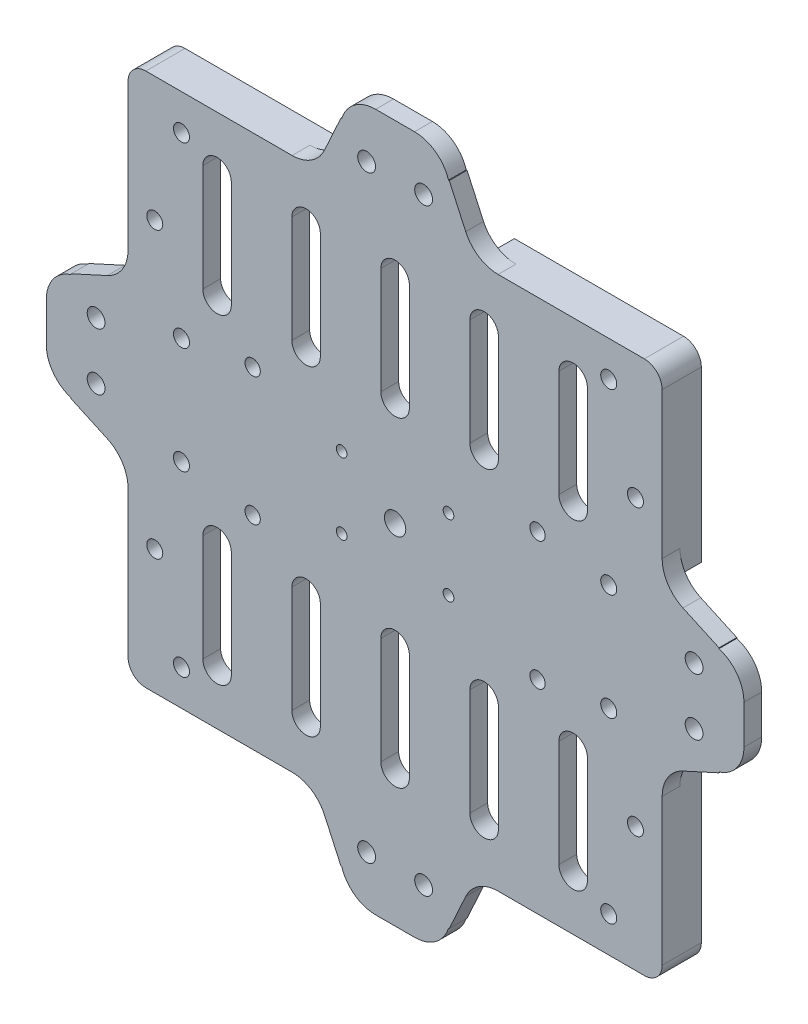
SolidWorks part; units mm, degrees
note: The reader was unsure of these and kept them because the rebuilt part matched: shared geometry of "Sketch1<4>".
material "ABS"
ref_plane "Front Plane" through (0, 0, 0) normal (0, 0, 1) x (1, 0, 0)
ref_plane "Top Plane" through (0, 0, 0) normal (0, 1, 0) x (1, 0, 0)
ref_plane "Right Plane" through (0, 0, 0) normal (1, 0, 0) x (0, 0, -1)
sketch "Sketch1" plane through (0, 0, 0) normal (0, 0, 1) x (1, 0, 0)
  line L13 (-90, -90) -> (90, -90)
  line L14 (-90, -90) -> (-90, 90)
  line L15 (-90, 90) -> (90, 90)
  line L16 (90, -90) -> (90, 90)
  line L17 (-90, -90) -> (90, 90) construction
  line L18 (-90, 90) -> (90, -90) construction
  line L19 (-75, -75) -> (75, -75)
  line L20 (-75, -75) -> (-75, 75)
  line L21 (-75, 75) -> (75, 75)
  line L22 (75, -75) -> (75, 75)
  line L23 (-75, -75) -> (75, 75) construction
  line L24 (-75, 75) -> (75, -75) construction
  line L39 (-75, -24.9122) -> (-75, 26.5574)
  line L40 (75, 22.5) -> (75, -22.5)
  line L41 (75, -22.5) -> (90.9698, -15.2063)
  line L42 (90.9698, -15.2063) -> (90.9698, 15.2063)
  line L43 (90.9698, 15.2063) -> (75, 22.5)
  line L44 (15.2063, -90.9698) -> (22.5, -75)
  line L45 (22.5, -75) -> (-22.5, -75)
  line L46 (-22.5, -75) -> (-15.2063, -90.9698)
  line L47 (-15.2063, -90.9698) -> (15.2063, -90.9698)
  line L48 (-90.9698, -15.2063) -> (-75, -22.5)
  line L49 (-75, -22.5) -> (-75, 22.5)
  line L50 (-75, 22.5) -> (-90.9698, 15.2063)
  line L51 (-90.9698, 15.2063) -> (-90.9698, -15.2063)
  line L52 (-15.2063, 90.9698) -> (-22.5, 75)
  line L53 (-22.5, 75) -> (22.5, 75)
  line L54 (22.5, 75) -> (15.2063, 90.9698)
  line L55 (15.2063, 90.9698) -> (-15.2063, 90.9698)
  line L64 (-72, -72) -> (-72, 72)
  line L65 (-72, 72) -> (72, 72)
  line L70 (72, -72) -> (72, 72)
  line L71 (-72, -72) -> (72, -72)
  line L72 (-10.5, -75) -> (10.5, -75)
  line L77 (75, -10.5) -> (64, -10.5)
  line L78 (75, -10.5) -> (75, 10.5)
  line L79 (75, 10.5) -> (64, 10.5)
  line L80 (64, -10.5) -> (64, 10.5)
  line L81 (-10.5, -75) -> (-10.5, -64)
  line L82 (-10.5, -64) -> (10.5, -64)
  line L83 (10.5, -75) -> (10.5, -64)
  line L84 (-75, 10.5) -> (-75, -10.5)
  line L85 (-75, 10.5) -> (-64, 10.5)
  line L86 (-64, 10.5) -> (-64, -10.5)
  line L87 (-75, -10.5) -> (-64, -10.5)
  line L88 (10.5, 75) -> (-10.5, 75)
  line L89 (10.5, 75) -> (10.5, 64)
  line L90 (10.5, 64) -> (-10.5, 64)
  line L91 (-10.5, 75) -> (-10.5, 64)
  line L92 (-75, 45) -> (-72, 45)
  line L93 (-45, 75) -> (-45, 72)
  line L94 (-75, 22.5) -> (-72, 22.5)
  line L95 (-75, -22.5) -> (-72, -22.5)
  line L96 (-22.5, 75) -> (-22.5, 72)
  line L97 (22.5, 75) -> (22.5, 72)
  line L98 (75, 22.5) -> (72, 22.5)
  line L99 (75, -22.5) -> (72, -22.5)
  line L100 (22.5, -75) -> (22.5, -72)
  line L101 (-22.5, -75) -> (-22.5, -72)
  circle A0 centre (83.9698, 8) radius 2.5
  circle A2 centre (83.9698, -8) radius 2.5
  circle A3 centre (8, -83.9698) radius 2.5
  circle A5 centre (-8, -83.9698) radius 2.5
  circle A6 centre (-83.9698, -8) radius 2.5
  circle A8 centre (-83.9698, 8) radius 2.5
  circle A9 centre (-8, 83.9698) radius 2.5
  circle A11 centre (8, 83.9698) radius 2.5
  circle A12 centre (0, 0) radius 3
  point P0 (0, 0)
  point P11 (0, 0)
  point P85 (0, 0)
  dimension "D3" = 4
  dimension "D12" = 6
  dimension "D1" = 180
  dimension "D2" = 180
  dimension "D4" = 150
  dimension "D5" = 4
  dimension "D6" = 3
  dimension "D8" = 11
  dimension "D7" = 21
  dimension "D10" = 45
  dimension "D11" = 45
  dimension "D9" = 4
  dimension "D13" = 4
extrude "Boss-Extrude1" add sketch "Sketch1" along normal mid plane 5 contours L91 L65 L64 L85 L86 L87 L71 L81 L82 L83 L70 L77 L80 L79 L89 L90 A12 | L39 L49 L50 L14 L48 A8 A6 | L94 L39 L85 L64 | L20 L94 L64 L92 | L39 L95 L64 L87 | L19 L101 L71 L64 L95 L20 | L19 L46 L13 L44 L45 A5 A3 | L101 L19 L81 L71 | L45 L83 L71 L81 | L71 L83 L82 L81 | L19 L100 L71 L83 | L100 L19 L22 L99 L70 L71 | L46 L47 L44 L13 | L99 L22 L77 L70 | L16 L43 L22 L40 L41 A2 A0 | L42 L43 L16 L41 | L40 L79 L70 L77 | L80 L77 L70 L79 | L22 L98 L70 L79 | L98 L22 L21 L97 L65 L70 | L97 L21 L89 L65 | L21 L53 L54 L15 L52 A11 A9 | L21 L96 L65 L91 | L53 L91 L65 L89 | L54 L55 L52 L15 | L96 L21 L93 L65 | L65 L91 L90 L89 | L93 L21 L20 L92 L64 L65 | L64 L87 L86 L85 | L49 L87 L64 L85 | L50 L51 L48 L14
extrude "Boss-Extrude3" add sketch "Sketch1<4>" against normal blind 6 from surface contours L93 L21 L20 L92 L64 L65 | L87 L39 L20 L19 L81 L71 L64 | L21 L89 L65 L70 L79 L22 | L83 L19 L22 L77 L70 L71 | L21 L93 L65 L91 | L92 L20 L39 L85 L64
sketch "Sketch1<4>" plane through (0, 0, 0) normal (0, 0, 1) x (1, 0, 0) same geometry as "Sketch1"
sketch "Sketch6" plane through (0, 0, 0) normal (0, 0, 1) x (1, 0, 0)
  line L0 (-25, 60) -> (-25, 30) construction
  line L12 (-40, 18) -> (40, 18) construction
  line L14 (6.05, 0) -> (-6.05, 0) construction
  line L15 (-40, -18) -> (40, -18) construction
  line L17 (-15, -10) -> (15, -10) construction
  line L18 (-15, -10) -> (-15, 10) construction
  line L19 (-15, 10) -> (15, 10) construction
  line L20 (15, -10) -> (15, 10) construction
  line L21 (-15, -10) -> (15, 10) construction
  line L22 (-15, 10) -> (15, -10) construction
  line L23 (-50, 60) -> (-50, 30) construction
  line L24 (-46, 60) -> (-46, 30)
  line L25 (-54, 60) -> (-54, 30)
  line L26 (-21, 60) -> (-21, 30)
  line L29 (-29, 60) -> (-29, 30)
  line L30 (0, 60) -> (0, 30) construction
  line L31 (4, 60) -> (4, 30)
  line L32 (-4, 60) -> (-4, 30)
  line L33 (25, 60) -> (25, 30) construction
  line L34 (29, 60) -> (29, 30)
  line L35 (21, 60) -> (21, 30)
  line L36 (50, 60) -> (50, 30) construction
  line L37 (54, 60) -> (54, 30)
  line L38 (46, 60) -> (46, 30)
  line L39 (116.8959, 0) -> (-116.8959, 0) construction
  line L40 (-50, -60) -> (-50, -30) construction
  line L41 (-46, -60) -> (-46, -30)
  line L42 (-54, -60) -> (-54, -30)
  line L43 (-25, -60) -> (-25, -30) construction
  line L44 (-21, -60) -> (-21, -30)
  line L45 (-29, -60) -> (-29, -30)
  line L46 (0, -60) -> (0, -30) construction
  line L47 (4, -60) -> (4, -30)
  line L48 (-4, -60) -> (-4, -30)
  line L49 (25, -60) -> (25, -30) construction
  line L50 (29, -60) -> (29, -30)
  line L51 (21, -60) -> (21, -30)
  line L52 (50, -60) -> (50, -30) construction
  line L53 (54, -60) -> (54, -30)
  line L54 (46, -60) -> (46, -30)
  circle A8 centre (40, 18) radius 2.15
  circle A9 centre (-40, 18) radius 2.15
  circle A10 centre (40, -18) radius 2.15
  circle A11 centre (-40, -18) radius 2.15
  circle A12 centre (-15, 10) radius 1.5
  circle A13 centre (-15, -10) radius 1.5
  circle A14 centre (15, -10) radius 1.5
  circle A15 centre (15, 10) radius 1.5
  arc A16 (-46, 60) -> (-54, 60) centre (-50, 60) ccw
  arc A17 (-54, 30) -> (-46, 30) centre (-50, 30) ccw
  arc A20 (-21, 60) -> (-29, 60) centre (-25, 60) ccw
  arc A21 (-29, 30) -> (-21, 30) centre (-25, 30) ccw
  arc A22 (4, 60) -> (-4, 60) centre (0, 60) ccw
  arc A23 (-4, 30) -> (4, 30) centre (0, 30) ccw
  arc A24 (29, 60) -> (21, 60) centre (25, 60) ccw
  arc A25 (21, 30) -> (29, 30) centre (25, 30) ccw
  arc A26 (54, 60) -> (46, 60) centre (50, 60) ccw
  arc A27 (46, 30) -> (54, 30) centre (50, 30) ccw
  arc A28 (-46, -60) -> (-54, -60) centre (-50, -60) cw
  arc A29 (-54, -30) -> (-46, -30) centre (-50, -30) cw
  arc A30 (-21, -60) -> (-29, -60) centre (-25, -60) cw
  arc A31 (-29, -30) -> (-21, -30) centre (-25, -30) cw
  arc A32 (4, -60) -> (-4, -60) centre (0, -60) cw
  arc A33 (-4, -30) -> (4, -30) centre (0, -30) cw
  arc A34 (29, -60) -> (21, -60) centre (25, -60) cw
  arc A35 (21, -30) -> (29, -30) centre (25, -30) cw
  arc A36 (54, -60) -> (46, -60) centre (50, -60) cw
  arc A37 (46, -30) -> (54, -30) centre (50, -30) cw
  point P3 (-25, 45)
  point P10 (0, 45)
  point P17 (25, 45)
  point P24 (50, 45)
  point P32 (0, 18)
  point P41 (0, 0)
  point P51 (-50, 45)
  point P60 (-50, -45)
  point P67 (-25, -45)
  point P74 (0, -45)
  point P81 (25, -45)
  point P88 (50, -45)
  dimension "D13" = 4.3
  dimension "D14" = 4.3
  dimension "D17" = 3
  dimension "D9" = 30
  dimension "D3" = 5
  dimension "D4" = 45
  dimension "D5" = 8
  dimension "D7" = 50
  dimension "D15" = 80
  dimension "D16" = 18
  dimension "D21" = 30
  dimension "D22" = 20
extrude "Cut-Extrude3" cut sketch "Sketch6" against normal mid plane 10
sketch "Sketch7" plane through (0, 0, 0) normal (0, 0, 1) x (1, 0, 0)
  line L0 (-90.9698, 15.2063) -> (-90.9698, -15.2063) construction
  line L1 (-97.9698, -15) -> (-90.9698, -15)
  line L2 (-97.9698, -15) -> (-97.9698, 15)
  line L3 (-97.9698, 15) -> (-90.9698, 15)
  line L4 (-90.9698, -15) -> (-90.9698, 15)
  line L5 (-97.9698, -15) -> (-90.9698, 15) construction
  line L6 (-97.9698, 15) -> (-90.9698, -15) construction
  line L7 (97.9698, -15) -> (90.9698, -15)
  line L8 (97.9698, -15) -> (97.9698, 15)
  line L9 (97.9698, 15) -> (90.9698, 15)
  line L10 (90.9698, -15) -> (90.9698, 15)
  line L11 (97.9698, -15) -> (90.9698, 15) construction
  line L12 (97.9698, 15) -> (90.9698, -15) construction
  line L17 (15.2063, 90.9698) -> (-15.2063, 90.9698) construction
  line L18 (-15, 97.9698) -> (15, 97.9698)
  line L19 (-15, 97.9698) -> (-15, 90.9698)
  line L20 (-15, 90.9698) -> (15, 90.9698)
  line L21 (15, 97.9698) -> (15, 90.9698)
  line L22 (-15, 97.9698) -> (15, 90.9698) construction
  line L23 (-15, 90.9698) -> (15, 97.9698) construction
  line L24 (15, -97.9698) -> (-15, -97.9698)
  line L25 (15, -97.9698) -> (15, -90.9698)
  line L26 (15, -90.9698) -> (-15, -90.9698)
  line L27 (-15, -97.9698) -> (-15, -90.9698)
  line L28 (15, -97.9698) -> (-15, -90.9698) construction
  line L29 (15, -90.9698) -> (-15, -97.9698) construction
  line L30 (90.9698, -15.2063) -> (90.9698, 15.2063) construction
  line L31 (-15.2063, -90.9698) -> (15.2063, -90.9698) construction
  point P0 (-94.4698, 0)
  point P6 (94.4698, 0)
  point P13 (0, -94.4698)
  point P17 (0, 94.4698)
  dimension "D1" = 7
  dimension "D2" = 30
  dimension "D3" = 7
  dimension "D4" = 7
  dimension "D5" = 7
  dimension "D6" = 30
  dimension "D7" = 30
  dimension "D8" = 30
extrude "Boss-Extrude4" add sketch "Sketch7" along normal up to surface (5 mm away) from surface at -2.5 contours L1 L4 L3 L2 | L21 L18 L19 L20 | L10 L7 L8 L9 | L27 L24 L25 L26 up to face at (25, -45, 2.5) starting at face at (25, -45, -2.5)
sketch "Sketch8" [suppressed] plane through (0, 0, 0) normal (0, 0, 1) x (1, 0, 0)
  line L0 (10.5, 75) -> (75, 75) construction
  line L1 (10.5, 72) -> (72, 72) construction
  line L2 (10.5, 75) -> (10.5, 72) construction
  line L3 (75, 10.5) -> (75, 75) construction
  line L4 (72, 10.5) -> (72, 72) construction
  line L5 (10.5, -75) -> (10.5, -72) construction
  line L6 (10.5, -72) -> (72, -72) construction
  line L7 (72, -72) -> (72, -10.5) construction
  line L8 (72, -10.5) -> (75, -10.5) construction
  line L9 (75, -10.5) -> (75, -75) construction
  line L10 (75, -75) -> (10.5, -75) construction
  line L11 (-75, -10.5) -> (-72, -10.5) construction
  line L12 (-72, -10.5) -> (-72, -72) construction
  line L13 (-72, -72) -> (-10.5, -72) construction
  line L14 (-10.5, -72) -> (-10.5, -75) construction
  line L15 (-10.5, -75) -> (-75, -75) construction
  line L16 (-75, -75) -> (-75, -10.5) construction
  line L17 (-72, 10.5) -> (-72, 72) construction
  line L18 (-75, 10.5) -> (-75, 75) construction
  line L19 (-10.5, 75) -> (-10.5, 72) construction
  line L20 (-72, 72) -> (-10.5, 72) construction
  line L21 (-75, 75) -> (-10.5, 75) construction
  line L22 (10.5, -75) -> (10.5, -72)
  line L23 (10.5, -72) -> (72, -72)
  line L24 (72, -72) -> (72, -10.5)
  line L25 (72, -10.5) -> (75, -10.5)
  line L26 (75, -10.5) -> (75, -75)
  line L27 (75, -75) -> (10.5, -75)
  line L28 (-75, -10.5) -> (-72, -10.5)
  line L29 (-72, -10.5) -> (-72, -72)
  line L30 (-72, -72) -> (-10.5, -72)
  line L31 (-10.5, -72) -> (-10.5, -75)
  line L32 (-10.5, -75) -> (-75, -75)
  line L33 (-75, -75) -> (-75, -10.5)
  line L34 (-72, 10.5) -> (-72, 72)
  line L35 (-75, 10.5) -> (-75, 75)
  line L36 (-10.5, 75) -> (-10.5, 72)
  line L37 (-72, 72) -> (-10.5, 72)
  line L38 (-75, 75) -> (-10.5, 75)
  line L39 (10.5, 75) -> (75, 75)
  line L40 (72, 10.5) -> (72, 72)
  line L41 (75, 10.5) -> (75, 75)
  line L42 (10.5, 75) -> (10.5, 72)
  line L43 (10.5, 72) -> (72, 72)
  line L44 (-75, 10.5) -> (-72, 10.5)
  line L45 (75, 10.5) -> (72, 10.5)
fillet "Fillet1" radius 10 16 edges at (22.5, -75, 0) (22.5, 75, 0) (75, 22.5, 0) (-75, -22.5, 0) (15, 97.9698, 0) (-15, 97.9698, 0) (-97.9698, 15, 0) (-97.9698, -15, 0) (-15, -97.9698, 0) (15, -97.9698, 0) (97.9698, -15, 0) (97.9698, 15, 0) (75, -22.5, 0) (-22.5, -75, 0) (-75, 22.5, 0) (-22.5, 75, 0)
fillet "Fillet2" [suppressed] radius 5
fillet "Fillet3" radius 5 4 edges at (75, 75, -3) (75, -75, -3) (-75, 75, -3) (-75, -75, -3)
sketch "Sketch9" plane through (0, 0, 0) normal (0, 0, 1) x (1, 0, 0)
  line L0 (67.5, 40) -> (-67.5, 40) construction
  line L1 (-60, 65) -> (60, 65) construction
  line L2 (-60, 65) -> (-60, 15) construction
  line L3 (-60, 15) -> (60, 15) construction
  line L4 (60, 65) -> (60, 15) construction
  line L5 (116.8959, 0) -> (-116.8959, 0) construction
  line L6 (-60, -65) -> (-60, -15) construction
  line L7 (-60, -15) -> (60, -15) construction
  line L8 (60, -65) -> (60, -15) construction
  line L9 (-60, -65) -> (60, -65) construction
  circle A0 centre (-60, 65) radius 2.25
  circle A1 centre (-60, 15) radius 2.25
  circle A2 centre (60, 15) radius 2.25
  circle A3 centre (60, 65) radius 2.25
  circle A4 centre (67.5, 40) radius 2.25
  circle A5 centre (-67.5, 40) radius 2.25
  circle A6 centre (-60, -15) radius 2.25
  circle A7 centre (60, -15) radius 2.25
  circle A8 centre (-60, -65) radius 2.25
  circle A9 centre (-67.5, -40) radius 2.25
  circle A10 centre (60, -65) radius 2.25
  circle A11 centre (67.5, -40) radius 2.25
  point P8 (0, 65)
  point P16 (-60, 40)
  point P17 (0, 40)
  dimension "D1" = 4.5
  dimension "D6" = 4.5
  dimension "D7" = 4.5
  dimension "D2" = 120
  dimension "D3" = 65
  dimension "D4" = 50
  dimension "D5" = 135
extrude "Cut-Extrude4" cut sketch "Sketch9" against normal mid plane 10
